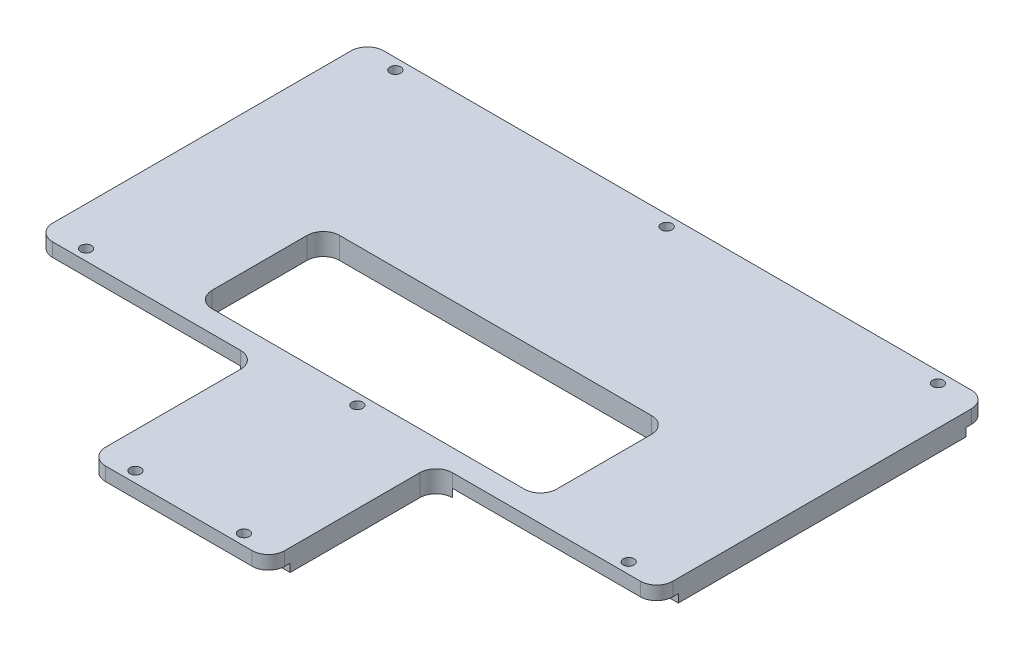
SolidWorks part; units mm, degrees
ref_plane "Plan de face" through (0, 0, 0) normal (0, 0, 1) x (1, 0, 0)
ref_plane "Plan de dessus" through (0, 0, 0) normal (0, 1, 0) x (1, 0, 0)
ref_plane "Plan de droite" through (0, 0, 0) normal (1, 0, 0) x (0, 0, -1)
sketch "Esquisse3" plane through (0, 0, 0) normal (0, 1, 0) x (1, 0, 0)
  line L0 (-57.15, -26.5) -> (57.15, -26.5)
  line L1 (-57.15, -30.5) -> (57.15, -30.5)
  line L2 (-57.15, -30.5) -> (-57.15, 30.5)
  line L3 (-57.15, 30.5) -> (57.15, 30.5)
  line L4 (57.15, -30.5) -> (57.15, 30.5)
  line L5 (-57.15, -30.5) -> (57.15, 30.5) construction
  line L6 (-57.15, 30.5) -> (57.15, -30.5) construction
  line L8 (-16.51, -30.5) -> (-16.51, -61.4)
  line L9 (-16.51, -61.4) -> (16.51, -61.4)
  line L10 (16.51, -30.5) -> (16.51, -61.4)
  line L11 (-16.51, -57.4) -> (16.51, -57.4)
  line L12 (-57.15, 26.5) -> (57.15, 26.5)
  line L13 (-57.15, 28.5) -> (57.15, 28.5) construction
  line L14 (-57.15, -28.5) -> (57.15, -28.5) construction
  line L15 (-16.51, -59.4) -> (16.51, -59.4) construction
  line L16 (-31.75, -26.5) -> (31.75, -26.5)
  line L17 (-31.75, -26.5) -> (-31.75, -3.0316)
  line L18 (-31.75, -3.0316) -> (31.75, -3.0316)
  line L19 (31.75, -26.5) -> (31.75, -3.0316)
  circle A0 centre (-50, 28.5) radius 1
  circle A1 centre (0, 28.5) radius 1
  circle A2 centre (50, 28.5) radius 1
  circle A3 centre (-50, -28.5) radius 1
  circle A4 centre (0, -28.5) radius 1
  circle A5 centre (50, -28.5) radius 1
  circle A6 centre (-10, -59.4) radius 1
  circle A7 centre (10, -59.4) radius 1
  point P0 (0, 0)
  dimension "D8" = 3
  dimension "D10" = 2
  dimension "D1" = 114.3
  dimension "D2" = 61
  dimension "D3" = 33.02
  dimension "D4" = 30.9
  dimension "D5" = 4
  dimension "D6" = 4
  dimension "D7" = 4
  dimension "D11" = 7.15
  dimension "D12" = 7.15
  dimension "D13" = 6.51
  dimension "D9" = 3
extrude "Boss.-Extru.1" add sketch "Esquisse3" along normal blind 4 contours L1 L4 L0 L2 A5 A4 A3 | L12 L2 L0 L4 | L8 L11 L10 L1 | L11 L8 L9 L10 A7 A6 | L2 L12 L4 L3 A2 A1 A0 region at (0, 0, -4.8175) region at (-44.45, 0, 27.6437) region at (-56.0063, 0, -28.5) region at (0, 0, 43.95) region at (0, 0, 59.4)
fillet "Congé1" radius 3 12 edges at (-57.15, 2, -30.5) (57.15, 2, -30.5) (57.15, 2, 30.5) (16.51, 2, 30.5) (16.51, 2, 61.4) (-16.51, 2, 61.4) (-16.51, 2, 30.5) (-57.15, 2, 30.5) (-31.75, 2, 3.0316) (31.75, 2, 3.0316) (31.75, 2, 26.5) (-31.75, 2, 26.5)
extrude "Enlèv. mat.-Extru.1" cut sketch "Esquisse3<3>" along normal blind 1.5 contours L1 L4 L0 L2 A5 A4 A3 | L11 L8 L9 L10 A7 A6 | L2 L12 L4 L3 A2 A1 A0 region at (-44.45, 0, 27.6437) region at (-56.0063, 0, -28.5) region at (0, 0, 59.4)
sketch "Esquisse3<3>" plane through (0, 0, 0) normal (0, 1, 0) x (1, 0, 0) same geometry as "Esquisse3"
